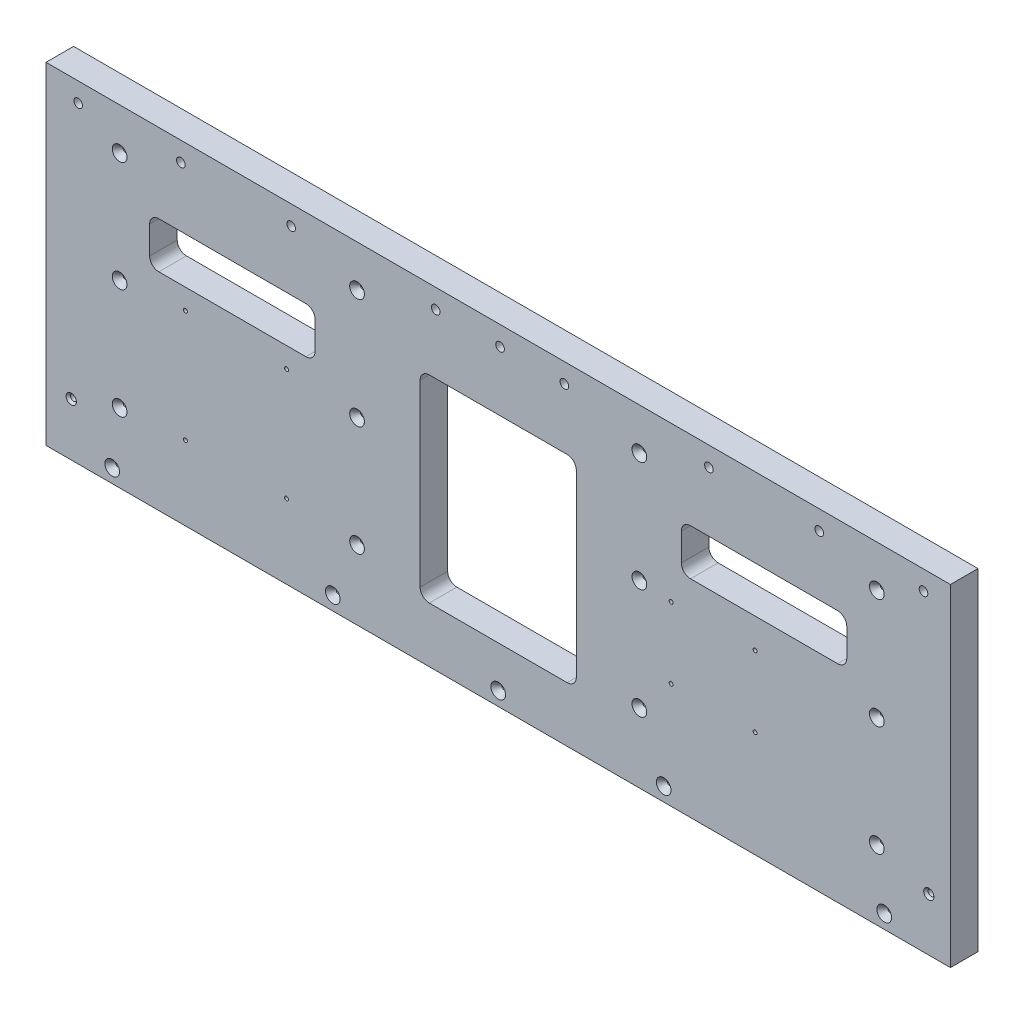
SolidWorks part; units mm, degrees
material "MDF"
ref_plane "Front Plane" through (0, 0, 0) normal (0, 0, 1) x (1, 0, 0)
ref_plane "Top Plane" through (0, 0, 0) normal (0, 1, 0) x (1, 0, 0)
ref_plane "Right Plane" through (0, 0, 0) normal (1, 0, 0) x (0, 0, -1)
sketch "Sketch1" plane through (0, 0, 0) normal (0, 0, 1) x (1, 0, 0)
  line L0 (128.7463, -697.8385) -> (128.7463, -132.715) construction
  line L1 (-496.0937, -132.715) -> (128.7463, -132.715)
  line L2 (-496.0937, -132.715) -> (-496.0937, -361.95)
  line L3 (-496.0937, -361.95) -> (128.7463, -361.95)
  line L4 (128.7463, -132.715) -> (128.7463, -361.95)
  line L5 (-496.0937, -132.715) -> (-496.0937, -697.8385) construction
  line L12 (128.7463, -132.715) -> (-84.6137, -132.715) construction
  line L13 (-290.722, -342.9) -> (-271.672, -342.9) construction
  dimension "D1" = 19.05
extrude "Boss-Extrude1" add sketch "Sketch1" along normal blind 19.05
hole_wizard "5/64 (0.07813) Diameter Hole1" positions "Sketch5" profile "Sketch6" hole size "5/64" standard "ANSI Inch"
sketch "Sketch5" plane through (-182.4037, -6471.4599, 19.05) normal (0, 0, 1) x (1, 0, 0)
  line L1 (-1.27, 6109.5099) -> (-1.27, 6338.7449) construction
  point P0 (-262.8265, 6157.4524)
  point P6 (-98.7933, 6157.4524)
  point P18 (-262.8265, 6233.6524)
  point P19 (-98.7933, 6233.6524)
  point P22 (-262.8265, 6309.8524)
  point P23 (-98.7933, 6309.8524)
  point P24 (-267.97, 6119.0349)
  point P34 (-115.57, 6119.0349)
  point P37 (-1.27, 6119.0349)
  point P40 (113.03, 6119.0349)
  point P44 (265.43, 6119.0349)
  point P55 (96.2533, 6309.8524)
  point P56 (260.2865, 6309.8524)
  point P59 (96.2533, 6233.6524)
  point P60 (260.2865, 6233.6524)
  point P63 (96.2533, 6157.4524)
  point P64 (260.2865, 6157.4524)
sketch "Sketch6" plane through (-445.2302, -314.0075, 19.05) normal (1, 0, 0) x (0, -1, 0)
  line L0 (0, 0) -> (0, 39.0539)
  line L1 (0, 39.0539) -> (1.5875, 38.1)
  line L2 (1.5875, 38.1) -> (1.5875, 4.0177)
  line L3 (1.5875, 4.0177) -> (5.08, 0)
  line L4 (5.08, 0) -> (0, 0)
  line L5 (-1.5875, 4.0177) -> (-5.08, 0) construction
  line L6 (0, 39.0539) -> (-1.5875, 38.1) construction
  line L7 (0, -6.35) -> (0, 107.95) construction
  dimension "Hole Dia." = 3.175
  dimension "Hole Depth" = 38.1
  dimension "Near C'Sink Dia." = 10.16
  dimension "Near C'Sink Angle" = 82
  dimension "Drill Angle" = 118
hole_wizard "15/64 (0.23438) Diameter Hole1" positions "Sketch7" profile "Sketch8" hole size "15/64" standard "ANSI Inch" end condition up to next
sketch "Sketch7" plane through (0, 0, 0) normal (0, 0, -1) x (-1, 0, 0)
  point P0 (402.9075, -146.05)
  point P2 (326.7075, -146.05)
  point P4 (226.8537, -146.05)
  point P6 (182.4037, -146.05)
  point P8 (137.9537, -146.05)
  point P10 (38.1, -146.05)
  point P12 (-38.1, -146.05)
  point P13 (473.8687, -146.05)
  point P17 (-110.1471, -146.05)
sketch "Sketch8" plane through (-402.9075, -146.05, 0) normal (1, 0, 0) x (0, 1, 0)
  line L0 (0, 0) -> (0, 19.05)
  line L1 (0, 19.05) -> (2.9766, 19.05)
  line L2 (2.9766, 19.05) -> (2.9766, 0)
  line L5 (2.9766, 0) -> (0, 0)
  line L11 (0, -6.35) -> (0, 107.95) construction
  dimension "Thru Hole Dia." = 5.9533
  dimension "Thru Hole Depth" = 19.05
sketch "Sketch9" plane through (0, 0, 0) normal (0, 0, -1) x (-1, 0, 0)
  line L0 (0, -157.1498) -> (0, -342.9) construction
  line L1 (0, -250.0249) -> (93.1355, -250.0249) construction
  line L2 (61.3728, -330.2) -> (-61.3728, -330.2)
  line L3 (61.3728, -330.2) -> (61.3728, -169.8498)
  line L4 (61.3728, -169.8498) -> (-61.3728, -169.8498)
  line L5 (-61.3728, -330.2) -> (-61.3728, -169.8498)
  line L6 (61.3728, -330.2) -> (-61.3728, -169.8498) construction
  line L7 (61.3728, -169.8498) -> (-61.3728, -330.2) construction
  line L8 (93.1355, -250.0249) -> (271.672, -250.0249) construction
  line L9 (364.8075, -157.1625) -> (364.8075, -342.9) construction
  line L10 (258.972, -330.2) -> (105.8355, -330.2)
  line L11 (258.972, -330.2) -> (258.972, -169.8498)
  line L12 (258.972, -169.8498) -> (105.8355, -169.8498)
  line L13 (105.8355, -330.2) -> (105.8355, -169.8498)
  line L14 (258.972, -330.2) -> (105.8355, -169.8498) construction
  line L15 (258.972, -169.8498) -> (105.8355, -330.2) construction
  line L17 (426.1802, -330.2127) -> (303.4347, -330.2127)
  line L18 (426.1802, -330.2127) -> (426.1802, -169.8498)
  line L19 (426.1802, -169.8498) -> (303.4347, -169.8498)
  line L20 (303.4347, -330.2127) -> (303.4347, -169.8498)
  line L21 (426.1802, -330.2127) -> (303.4347, -169.8498) construction
  line L22 (426.1802, -169.8498) -> (303.4347, -330.2127) construction
  point P3 (0, -250.0249)
  point P8 (-74.0728, -342.9)
  point P13 (182.4037, -250.0249)
  point P20 (364.8075, -250.0313)
  dimension "D1" = 12.7
  dimension "D2" = 12.7
  dimension "D3" = 12.7
extrude "Cut-Extrude1" [suppressed] cut sketch "Sketch9" against normal up to next
fillet "Fillet1" [suppressed] radius 12.7
hole_wizard "#2 Clearance Hole1" positions "Sketch10" profile "Sketch11" hole size "#2" standard "ANSI Inch" end condition up to next
sketch "Sketch10" plane through (0, 0, 19.05) normal (0, 0, 1) x (1, 0, 0)
  point P2 (-6.2354, -239.6)
  point P4 (-64.2354, -239.6)
  point P6 (-64.2354, -288.6)
  point P8 (-6.2354, -288.6)
sketch "Sketch11" plane through (-6.2354, -239.6, 19.05) normal (1, 0, 0) x (0, -1, 0)
  line L0 (0, 0) -> (0, 19.05)
  line L1 (0, 19.05) -> (1.3525, 19.05)
  line L2 (1.3525, 19.05) -> (1.3525, 0)
  line L5 (1.3525, 0) -> (0, 0)
  line L11 (0, -6.35) -> (0, 107.95) construction
  dimension "Thru Hole Dia." = 2.7051
  dimension "Thru Hole Depth" = 19.05
hole_wizard "#2 Clearance Hole2" positions "Sketch12" profile "Sketch13" hole size "#2" standard "ANSI Inch" end condition up to next
sketch "Sketch12" plane through (0, 0, 0) normal (0, 0, -1) x (-1, 0, 0)
  point P0 (399.7261, -233.172)
  point P2 (329.8761, -233.172)
  point P4 (329.8761, -310.642)
  point P6 (399.7261, -310.642)
sketch "Sketch13" plane through (-399.7261, -233.172, 0) normal (1, 0, 0) x (0, 1, 0)
  line L0 (0, 0) -> (0, 19.05)
  line L1 (0, 19.05) -> (1.3525, 19.05)
  line L2 (1.3525, 19.05) -> (1.3525, 0)
  line L5 (1.3525, 0) -> (0, 0)
  line L11 (0, -6.35) -> (0, 107.95) construction
  dimension "Thru Hole Dia." = 2.7051
  dimension "Thru Hole Depth" = 19.05
hole_wizard "CSK for #6 Flat Head Machine Screw (100)1" positions "Sketch16" profile "Sketch17" countersink size "#6" standard "ANSI Inch" end condition up to next
sketch "Sketch16" plane through (0, 0, 19.05) normal (0, 0, 1) x (1, 0, 0)
  point P6 (113.8236, -325.4344)
  point P8 (-478.6312, -325.4375)
sketch "Sketch17" plane through (113.8236, -325.4344, 19.05) normal (1, 0, 0) x (0, -1, 0)
  line L0 (0, 0) -> (0, 19.05)
  line L1 (0, 19.05) -> (2.1526, 19.05)
  line L2 (2.1526, 19.05) -> (2.1526, 1.5998)
  line L3 (2.1526, 1.5998) -> (3.5433, 0)
  line L5 (3.5433, 0) -> (0, 0)
  line L6 (-2.1526, 1.5998) -> (-3.5433, 0) construction
  line L11 (0, -6.35) -> (0, 107.95) construction
  dimension "Thru Hole Dia." = 4.3053
  dimension "Thru Hole Depth" = 19.05
  dimension "Near C'Sink Dia." = 7.0866
  dimension "Near C'Sink Angle" = 82
sketch "Sketch18" plane through (0, 0, 0) normal (0, 0, -1) x (-1, 0, 0)
  line L0 (-74.0728, -171.45) -> (74.0855, -171.45) construction
  line L1 (-57.1437, -187.325) -> (57.1563, -187.325)
  line L2 (-57.1437, -187.325) -> (-57.1437, -219.075)
  line L3 (-57.1437, -219.075) -> (57.1563, -219.075)
  line L4 (57.1563, -187.325) -> (57.1563, -219.075)
  line L5 (-57.1437, -187.325) -> (57.1563, -219.075) construction
  line L6 (-57.1437, -219.075) -> (57.1563, -187.325) construction
  line L7 (496.0937, -361.95) -> (-128.7463, -361.95) construction
  line L8 (183.6737, -361.95) -> (183.6737, -132.715) construction
  line L9 (-128.7463, -132.715) -> (496.0937, -132.715) construction
  line L10 (424.4911, -187.325) -> (424.4911, -219.075)
  line L11 (424.4911, -219.075) -> (310.1911, -219.075)
  line L12 (310.1911, -187.325) -> (310.1911, -219.075)
  line L13 (424.4911, -187.325) -> (310.1911, -187.325)
  line L15 (237.6487, -323.85) -> (129.6987, -323.85)
  line L16 (237.6487, -323.85) -> (237.6487, -187.325)
  line L17 (237.6487, -187.325) -> (129.6987, -187.325)
  line L18 (129.6987, -323.85) -> (129.6987, -187.325)
  line L19 (237.6487, -323.85) -> (129.6987, -187.325) construction
  line L20 (237.6487, -187.325) -> (129.6987, -323.85) construction
  point P4 (0.0063, -203.2)
  point P8 (0.0063, -171.45)
  point P19 (183.6737, -255.5875)
  dimension "D1" = 114.3
  dimension "D2" = 31.75
  dimension "D3" = 158.75
  dimension "D4" = 38.1
  dimension "D6" = 107.95
extrude "Cut-Extrude2" cut sketch "Sketch18" against normal up to next
fillet "Fillet2" radius 6.35 12 edges at (-310.1911, -187.325, 9.525) (-310.1911, -219.075, 9.525) (-424.4911, -219.075, 9.525) (-424.4911, -187.325, 9.525) (-237.6487, -187.325, 9.525) (-237.6487, -323.85, 9.525) (-129.6987, -323.85, 9.525) (-129.6987, -187.325, 9.525) (-57.1563, -187.325, 9.525) (-57.1563, -219.075, 9.525) (57.1437, -219.075, 9.525) (57.1437, -187.325, 9.525)
